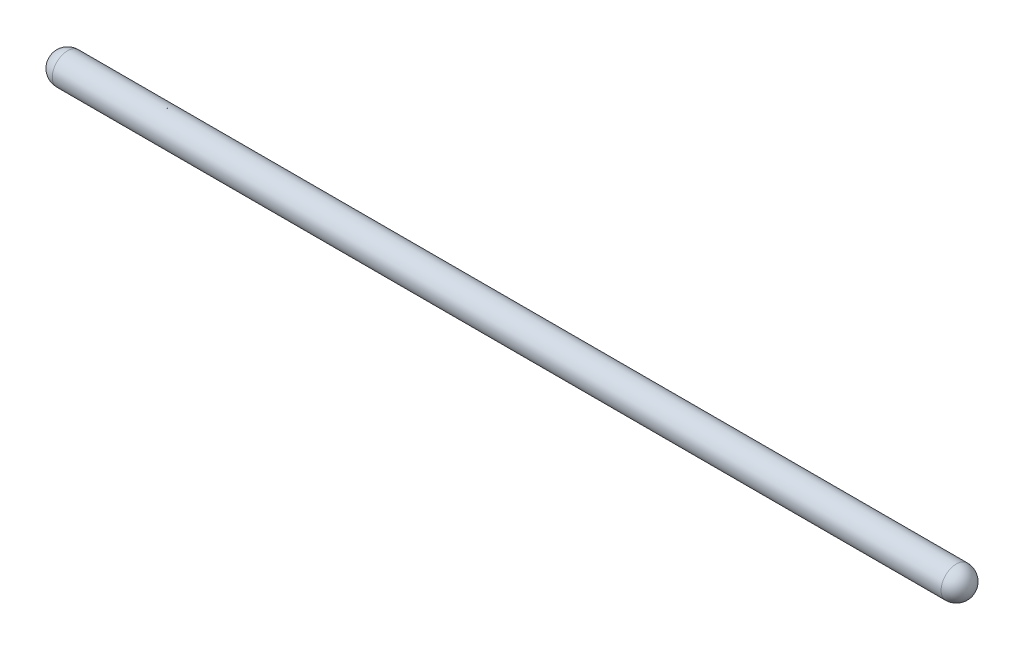
SolidWorks part; units mm, degrees
material "Brass"
ref_plane "Front Plane" through (0, 0, 0) normal (0, 0, 1) x (1, 0, 0)
ref_plane "Top Plane" through (0, 0, 0) normal (0, 1, 0) x (1, 0, 0)
ref_plane "Right Plane" through (0, 0, 0) normal (1, 0, 0) x (0, 0, -1)
sketch "Sketch1" plane through (0, 0, 0) normal (0, 0, 1) x (1, 0, 0)
  line L0 (0, 0) -> (150, 0) construction
  line L1 (2.5, 2.5) -> (147.5, 2.5)
  line L2 (150, 0) -> (0, 0)
  arc A0 (150, 0) -> (147.5, 2.5) centre (147.5, 0) ccw
  arc A1 (2.5, 2.5) -> (0, 0) centre (2.5, 0) ccw
  dimension "D3" = 2.5
  dimension "D1" = 2.5
  dimension "D2" = 147.5
revolve "Revolve1" add sketch "Sketch1" angle 360 about L0
